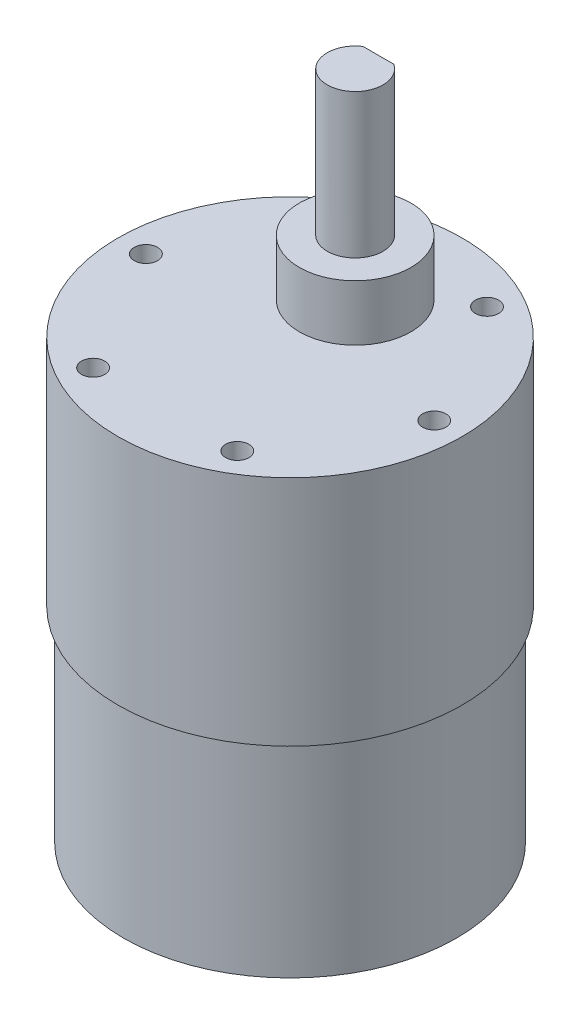
SolidWorks part; units mm, degrees
ref_plane "Front Plane" through (0, 0, 0) normal (0, 0, 1) x (1, 0, 0)
ref_plane "Top Plane" through (0, 0, 0) normal (0, 1, 0) x (1, 0, 0)
ref_plane "Right Plane" through (0, 0, 0) normal (1, 0, 0) x (0, 0, -1)
sketch "Sketch1" plane through (0, 0, 0) normal (0, 1, 0) x (1, 0, 0)
  circle A0 centre (0, 0) radius 18.5
  dimension "D1" = 37
extrude "Boss-Extrude1" add sketch "Sketch1" along normal blind 25
sketch "Sketch2" plane through (0, 25, 0) normal (0, 1, 0) x (1, 0, 0)
  circle A0 centre (0, 7) radius 6
  dimension "D2" = 12
  dimension "D1" = 7
extrude "Boss-Extrude2" add sketch "Sketch2" along normal blind 6
sketch "Sketch3" plane through (0, 31, 0) normal (0, 1, 0) x (1, 0, 0)
  line L0 (-1.6583, 9.5) -> (1.6583, 9.5)
  arc A0 (-1.6583, 9.5) -> (1.6583, 9.5) centre (0, 7) ccw
  arc A1 (1.6583, 9.5) -> (-1.6583, 9.5) centre (0, 7) ccw
  dimension "D1" = 6
  dimension "D2" = 2.5
extrude "Boss-Extrude3" add sketch "Sketch3" along normal blind 15.5 contours L0 A0 region at (0, 31, -6.888)
extrude "Boss-Extrude4" add sketch "Sketch3<3>" along normal blind 6 contours L0 A1 region at (0, 31, -9.7015)
sketch "Sketch3<3>" plane through (0, 31, 0) normal (0, 1, 0) x (1, 0, 0) same geometry as "Sketch3"
sketch "Sketch4" plane through (0, 25, 0) normal (0, 1, 0) x (1, 0, 0)
  circle A0 centre (0, 0) radius 15.5 construction
  point P3 (-15.5, 0)
  point P6 (-7.75, 13.4234)
  point P7 (7.75, 13.4234)
  point P8 (15.5, 0)
  point P9 (7.75, -13.4234)
  point P10 (-7.75, -13.4234)
  point P11 (0, 0)
  dimension "D1" = 31
  dimension "D2" = 6
hole_wizard "Tap Drill for M3x0.5 Tap1" positions "Sketch5" profile "Sketch6" hole size "M3x0.5" standard "ANSI Metric"
sketch "Sketch5" plane through (0, 25, 0) normal (0, 1, 0) x (1, 0, 0)
  point P0 (-15.5, 0)
  point P3 (-7.75, 13.4234)
  point P6 (7.75, 13.4234)
  point P9 (15.5, 0)
  point P12 (7.75, -13.4234)
  point P15 (-7.75, -13.4234)
sketch "Sketch6" plane through (-15.5, 25, 0) normal (1, 0, 0) x (0, 0, 1)
  line L0 (0, 0) -> (0, 4.2511)
  line L1 (0, 4.2511) -> (1.25, 3.5)
  line L2 (1.25, 3.5) -> (1.25, 0)
  line L5 (1.25, 0) -> (0, 0)
  line L10 (0, 4.2511) -> (-1.25, 3.5) construction
  line L11 (0, -6.35) -> (0, 107.95) construction
  dimension "Hole Dia." = 2.5
  dimension "Hole Depth" = 3.5
  dimension "Drill Angle" = 118
sketch "Sketch7" plane through (0, 0, 0) normal (0, -1, 0) x (1, 0, 0)
  circle A0 centre (0, 0) radius 17.9
  dimension "D1" = 35.8
extrude "Boss-Extrude5" add sketch "Sketch7" along normal blind 22
equation "\"D1@Sketch1\"=37MM"
equation "\"D1@Boss-Extrude1\"=25MM"
equation "\"D1@Sketch2\"=7mm"
equation "\"D2@Sketch2\"=12mm"
equation "\"D1@Boss-Extrude2\"=6mm"
equation "\"D1@Sketch3\"=6mm"
equation "\"D1@Boss-Extrude3\"=15.5mm"
equation "\"D2@Sketch3\"=2.5mm"
equation "\"D1@Boss-Extrude4\"=6mm"
equation "\"D1@Sketch4\"=31mm"
equation "\"D1@Sketch7\"=35.8MM"
equation "\"D1@Boss-Extrude5\"=22mm"
